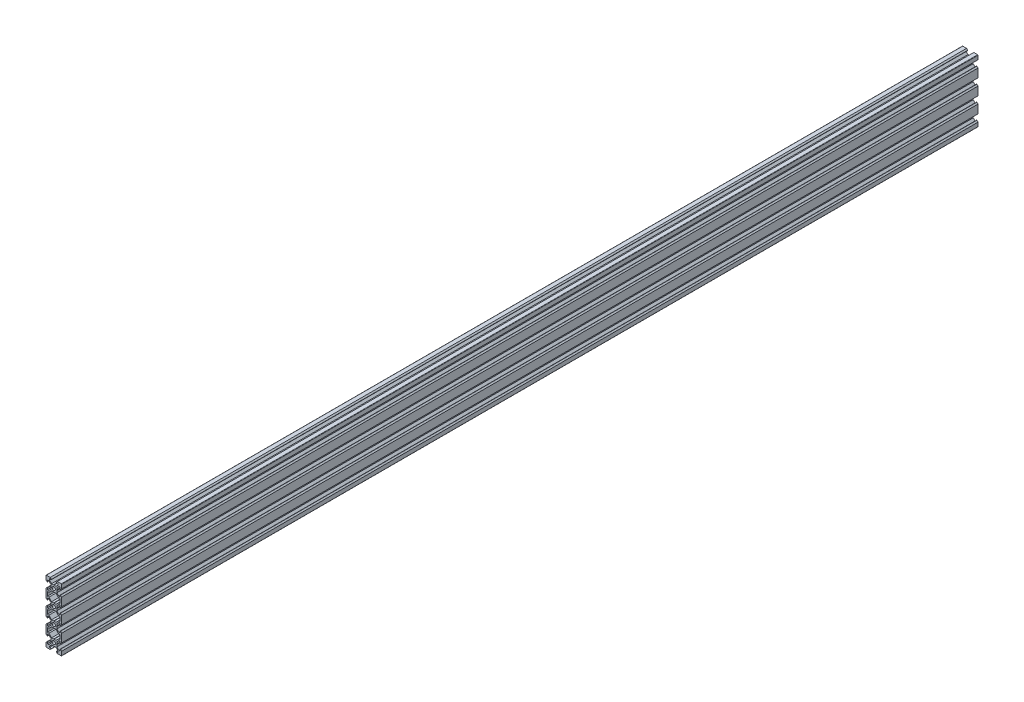
SolidWorks part; units mm, degrees
ref_plane "Plan de face" through (0, 0, 0) normal (0, 0, 1) x (1, 0, 0)
ref_plane "Plan de dessus" through (0, 0, 0) normal (0, 1, 0) x (1, 0, 0)
ref_plane "Plan de droite" through (0, 0, 0) normal (1, 0, 0) x (0, 0, -1)
ref_axis "Axe" through (0, 0, -13.782) along (0, 0, 1)
sketch "Esquisse1" plane through (0, 0, 0) normal (0, 0, 1) x (1, 0, 0)
  line L0 (0, 27.6392) -> (0, -27.6392) construction
  line L1 (-33.6074, 0) -> (33.6074, 0) construction
  line L2 (0, 0) -> (-22.2114, 22.2114) construction
  line L3 (-9.5, 10) -> (-4.58, 10)
  line L4 (-4.58, 10) -> (-3.125, 8.545)
  line L5 (-3.125, 8.545) -> (-3.125, 8.2)
  line L6 (-3.125, 8.2) -> (-5.5, 8.2)
  line L7 (-2.8393, 3.9) -> (-5.5, 6.5607)
  line L8 (-2.8393, 3.9) -> (-0.21, 3.9)
  line L9 (-5.5, 6.5607) -> (-5.5, 8.2)
  line L10 (0, 3.69) -> (0, 2.1)
  line L11 (-3.9, 2.8393) -> (-6.5607, 5.5)
  line L12 (-8.545, 3.125) -> (-8.2, 3.125)
  line L13 (-8.2, 3.125) -> (-8.2, 5.5)
  line L14 (-6.5607, 5.5) -> (-8.2, 5.5)
  line L15 (-10, 4.58) -> (-8.545, 3.125)
  line L16 (-10, 9.5) -> (-10, 4.58)
  line L17 (-0.21, 3.9) -> (0, 3.69)
  line L18 (-3.9, 2.8393) -> (-3.9, 0.21)
  line L19 (-6.2393, -12.7) -> (-8.2, -12.7)
  line L20 (-3.9, 0.21) -> (-3.69, 0)
  line L21 (-0.21, -3.9) -> (0, -3.69)
  line L22 (0, -3.69) -> (0, -2.1)
  line L23 (-6.5607, -5.5) -> (-8.2, -5.5)
  line L24 (-2.8393, -3.9) -> (-0.21, -3.9)
  line L25 (-8.545, -3.125) -> (-8.2, -3.125)
  line L26 (-10, -4.58) -> (-8.545, -3.125)
  line L27 (-8.2, -3.125) -> (-8.2, -5.5)
  line L28 (-2.8393, -3.9) -> (-6.2393, -7.3)
  line L29 (-3.9, -2.8393) -> (-6.5607, -5.5)
  line L30 (-3.9, -2.8393) -> (-3.9, -0.21)
  line L31 (-3.9, -0.21) -> (-3.69, 0)
  line L32 (-6.2393, -7.3) -> (-8.2, -7.3)
  line L33 (-8.2, -7.3) -> (-8.2, -12.7)
  line L34 (-8.2, -10) -> (-10, -10) construction
  line L35 (-10, -15.42) -> (-10, -4.58)
  line L36 (-3.9, -19.79) -> (-3.69, -20)
  line L37 (-3.9, -17.1607) -> (-3.9, -19.79)
  line L38 (-3.9, -17.1607) -> (-6.5607, -14.5)
  line L39 (-2.8393, -16.1) -> (-6.2393, -12.7)
  line L40 (-8.2, -16.875) -> (-8.2, -14.5)
  line L41 (-10, -15.42) -> (-8.545, -16.875)
  line L42 (-8.545, -16.875) -> (-8.2, -16.875)
  line L43 (-2.8393, -16.1) -> (-0.21, -16.1)
  line L44 (-6.5607, -14.5) -> (-8.2, -14.5)
  line L45 (0, -16.31) -> (0, -17.9)
  line L46 (-0.21, -16.1) -> (0, -16.31)
  line L47 (-8.2, -30) -> (-10, -30) construction
  line L48 (-3.69, -20) -> (0, -20) construction
  line L49 (-0.21, -23.9) -> (0, -23.69)
  line L50 (0, -23.69) -> (0, -22.1)
  line L51 (-6.5607, -25.5) -> (-8.2, -25.5)
  line L52 (-2.8393, -23.9) -> (-0.21, -23.9)
  line L53 (-8.545, -23.125) -> (-8.2, -23.125)
  line L54 (-10, -24.58) -> (-8.545, -23.125)
  line L55 (-8.2, -23.125) -> (-8.2, -25.5)
  line L56 (-2.8393, -23.9) -> (-6.2393, -27.3)
  line L57 (-3.9, -22.8393) -> (-6.5607, -25.5)
  line L58 (-3.9, -22.8393) -> (-3.9, -20.21)
  line L59 (-3.9, -20.21) -> (-3.69, -20)
  line L60 (-10, -24.58) -> (-10, -35.42)
  line L61 (-8.2, -32.7) -> (-8.2, -27.3)
  line L62 (-3.69, -40) -> (0, -40) construction
  line L63 (-8.2, -50) -> (-10, -50) construction
  line L64 (0, -60) -> (-22.2114, -82.2114) construction
  line L65 (-33.6074, -60) -> (33.6074, -60) construction
  line L66 (0, -87.6392) -> (0, -32.3608) construction
  line L67 (-6.2393, -32.7) -> (-8.2, -32.7)
  line L68 (-3.9, -39.79) -> (-3.69, -40)
  line L69 (-3.9, -37.1607) -> (-3.9, -39.79)
  line L70 (-3.9, -37.1607) -> (-6.5607, -34.5)
  line L71 (-2.8393, -36.1) -> (-6.2393, -32.7)
  line L72 (-8.2, -36.875) -> (-8.2, -34.5)
  line L73 (-10, -35.42) -> (-8.545, -36.875)
  line L74 (-8.545, -36.875) -> (-8.2, -36.875)
  line L75 (-6.2393, -27.3) -> (-8.2, -27.3)
  line L76 (-2.8393, -36.1) -> (-0.21, -36.1)
  line L77 (-6.5607, -34.5) -> (-8.2, -34.5)
  line L78 (0, -36.31) -> (0, -37.9)
  line L79 (-0.21, -36.1) -> (0, -36.31)
  line L80 (-0.21, -43.9) -> (0, -43.69)
  line L81 (0, -43.69) -> (0, -42.1)
  line L82 (-6.5607, -45.5) -> (-8.2, -45.5)
  line L83 (-2.8393, -43.9) -> (-0.21, -43.9)
  line L84 (-8.545, -43.125) -> (-8.2, -43.125)
  line L85 (-10, -44.58) -> (-8.545, -43.125)
  line L86 (-8.2, -43.125) -> (-8.2, -45.5)
  line L87 (-2.8393, -43.9) -> (-6.2393, -47.3)
  line L88 (-3.9, -42.8393) -> (-6.5607, -45.5)
  line L89 (-3.9, -42.8393) -> (-3.9, -40.21)
  line L90 (-3.9, -40.21) -> (-3.69, -40)
  line L91 (-10, -44.58) -> (-10, -55.42)
  line L92 (-8.2, -52.7) -> (-8.2, -47.3)
  line L93 (-6.2393, -52.7) -> (-8.2, -52.7)
  line L94 (-3.9, -59.79) -> (-3.69, -60)
  line L95 (-3.9, -57.1607) -> (-3.9, -59.79)
  line L96 (-3.9, -57.1607) -> (-6.5607, -54.5)
  line L97 (-2.8393, -56.1) -> (-6.2393, -52.7)
  line L98 (-8.2, -56.875) -> (-8.2, -54.5)
  line L99 (-10, -55.42) -> (-8.545, -56.875)
  line L100 (-8.545, -56.875) -> (-8.2, -56.875)
  line L101 (-2.8393, -56.1) -> (-0.21, -56.1)
  line L102 (-6.5607, -54.5) -> (-8.2, -54.5)
  line L103 (0, -56.31) -> (0, -57.9)
  line L104 (-0.21, -56.1) -> (0, -56.31)
  line L105 (-3.9, -60.21) -> (-3.69, -60)
  line L106 (-6.2393, -47.3) -> (-8.2, -47.3)
  line L107 (-3.9, -62.8393) -> (-3.9, -60.21)
  line L108 (-0.21, -63.9) -> (0, -63.69)
  line L109 (-10, -69.5) -> (-10, -64.58)
  line L110 (-10, -64.58) -> (-8.545, -63.125)
  line L111 (-6.5607, -65.5) -> (-8.2, -65.5)
  line L112 (-8.2, -63.125) -> (-8.2, -65.5)
  line L113 (-8.545, -63.125) -> (-8.2, -63.125)
  line L114 (-3.9, -62.8393) -> (-6.5607, -65.5)
  line L115 (0, -63.69) -> (0, -62.1)
  line L116 (-5.5, -66.5607) -> (-5.5, -68.2)
  line L117 (-2.8393, -63.9) -> (-0.21, -63.9)
  line L118 (-2.8393, -63.9) -> (-5.5, -66.5607)
  line L119 (-3.125, -68.2) -> (-5.5, -68.2)
  line L120 (-3.125, -68.545) -> (-3.125, -68.2)
  line L121 (-4.58, -70) -> (-3.125, -68.545)
  line L122 (-9.5, -70) -> (-4.58, -70)
  arc A0 (0, -2.1) -> (0, 2.1) centre (0, 0) cw
  arc A1 (-9.5, 10) -> (-10, 9.5) centre (-9.5, 9.5) ccw
  arc A2 (0, -42.1) -> (0, -37.9) centre (0, -40) cw
  arc A3 (-9.5, -70) -> (-10, -69.5) centre (-9.5, -69.5) cw
  arc A4 (0, -17.9) -> (0, -22.1) centre (0, -20) ccw
  arc A5 (0, -57.9) -> (0, -62.1) centre (0, -60) ccw
  point P4 (0, 0)
  point P7 (0, 0)
  point P30 (-10, 10)
  point P60 (0, -20)
  point P146 (-10, -70)
  dimension "D5" = 11
  dimension "D2" = 2.1
  dimension "D3" = 6.25
  dimension "D10" = 0.5
  dimension "D4" = 9.16
  dimension "D6" = 1.5
  dimension "D7" = 1.8
  dimension "D8" = 4.3
  dimension "D9" = 20
  dimension "D11" = 0.42
  dimension "D12" = 10
  dimension "D13" = 1.8
extrude "Boss.-Extru.1" add sketch "Esquisse1" along normal blind 1173.42
sketch "Esquisse3" plane through (0, 0, 1173.42) normal (0, 0, 1) x (1, 0, 0)
  line L0 (0, 0) -> (-9.8536, 9.8536) construction
  line L1 (-8.2, 8.2) -> (-8.2, 6.57)
  line L2 (-8.2, 6.57) -> (-7.54, 6.57)
  line L3 (-7.54, 6.57) -> (-6.57, 7.54)
  line L4 (-8.2, 3.125) -> (-8.2, 5.5) construction
  line L5 (-6.57, 8.2) -> (-6.57, 7.54)
  line L6 (-8.2, 8.2) -> (-6.57, 8.2)
  line L7 (-5.5, 6.5607) -> (-5.5, 8.2) construction
  line L8 (-10, -30) -> (6.918, -30) construction
  line L9 (-10, -24.58) -> (-10, -35.42) construction
  line L10 (-8.2, -68.2) -> (-6.57, -68.2)
  line L11 (-6.57, -68.2) -> (-6.57, -67.54)
  line L12 (-7.54, -66.57) -> (-6.57, -67.54)
  line L13 (-8.2, -66.57) -> (-7.54, -66.57)
  line L14 (-8.2, -68.2) -> (-8.2, -66.57)
  arc A0 (-9.5, 10) -> (-10, 9.5) centre (-9.5, 9.5) ccw construction
  point P13 (-7.055, 7.055)
  point P14 (-6.57, 7.87)
  point P26 (-7.055, -67.055)
  dimension "D1" = 1.07
extrude "Enlèv. mat.-Extru.1" [suppressed] cut sketch "Esquisse3" against normal through all
mirror "Symétrie1" about plane through (0, 3.69, 1173.42) normal (-1, 0, 0) of "Enlèv. mat.-Extru.1", "Boss.-Extru.1"
